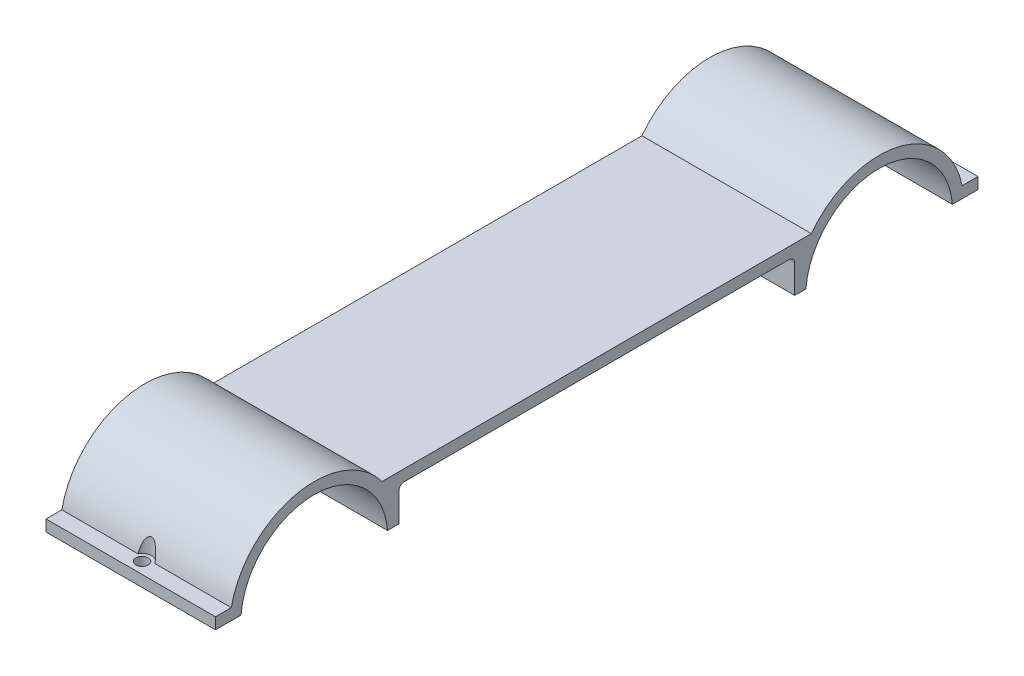
SolidWorks part; units mm, degrees
ref_plane "Спереди" through (0, 0, 0) normal (0, 0, 1) x (1, 0, 0)
ref_plane "Сверху" through (0, 0, 0) normal (0, 1, 0) x (1, 0, 0)
ref_plane "Справа" through (0, 0, 0) normal (1, 0, 0) x (0, 0, -1)
sketch "Эскиз1" plane through (0, 0, 0) normal (1, 0, 0) x (0, 0, -1)
  line L0 (-67.5, 0) -> (67.5, 0) construction
  line L1 (-67.5, 3) -> (-67.5, 1)
  line L2 (-67.5, 1) -> (-62.9615, 1)
  line L3 (-35.0385, 7) -> (-35.0385, 1)
  line L4 (62.9615, 1) -> (67.5, 1)
  line L5 (67.5, 1) -> (67.5, 3)
  line L6 (-67.5, 3) -> (-64.6969, 3)
  line L7 (-35.0385, 1) -> (-37.0385, 1)
  line L8 (64.6969, 3) -> (67.5, 3)
  line L9 (50, 13.2) -> (-50, 13.2) construction
  line L10 (-67.5, 1) -> (88.9784, 1) construction
  line L11 (-35.0385, 7) -> (35.0385, 7)
  line L12 (35.0385, 7) -> (35.0385, 1)
  line L13 (-38, 9) -> (38, 9)
  line L14 (35.0385, 1) -> (37.0385, 1)
  arc A0 (-62.9615, 1) -> (-37.0385, 1) centre (-50, 0) cw
  arc A1 (62.9615, 1) -> (37.0385, 1) centre (50, 0) ccw
  arc A2 (-64.6969, 3) -> (-38, 9) centre (-50, 0) cw
  arc A3 (64.6969, 3) -> (38, 9) centre (50, 0) ccw
  dimension "D5" = 1
  dimension "D6" = 1
  dimension "D9" = 2
  dimension "D10" = 2
  dimension "D13" = 2
  dimension "D14" = 13
  dimension "D15" = 13
  dimension "D2" = 15
  dimension "D16" = 15
  dimension "D1" = 135
  dimension "D3" = 17.5
  dimension "D4" = 17.5
  dimension "D7" = 2
  dimension "3" = 3
  dimension "D8" = 3
  dimension "D11" = 25.923
  dimension "D12" = 25.923
  dimension "D17" = 76
  dimension "D18" = 67.5
extrude "Бобышка-Вытянуть1" add sketch "Эскиз1" along normal blind 15 and the other way blind 15
fillet "Скругление4" radius 1 2 edges at (0, 7, -35.0385) (0, 7, 35.0385)
sketch "Эскиз2" plane through (0, 3, 0) normal (0, 1, 0) x (1, 0, 0)
  line L1 (-15, 67.5) -> (15, 67.5) construction
  circle A0 centre (0, 65.5) radius 1.1
  dimension "D2" = 2.2
  dimension "D1" = 2
extrude "Вырез-Вытянуть1" cut sketch "Эскиз2" against normal blind 10 and the other way blind 10
sketch "Эскиз3" plane through (0, 3, 0) normal (0, 1, 0) x (1, 0, 0)
  line L0 (-15, 64.6969) -> (-0.7517, 64.6969) construction
  line L1 (-15, 62.9615) -> (15, 62.9615) construction
  line L2 (-15, 67.5) -> (-15, 64.6969) construction
  circle A0 centre (0, 65.5) radius 1.7035
  point P9 (-15, 66.0985)
  dimension "D1" = 0.8031
  dimension "D2" = 2.5385
  dimension "D3" = 15
extrude "Вырез-Вытянуть2" cut sketch "Эскиз3" along normal blind 10
mirror "Зеркальное отражение1" about plane through (0, 0, 0) normal (0, 0, 1) of "Вырез-Вытянуть2", "Вырез-Вытянуть1"
